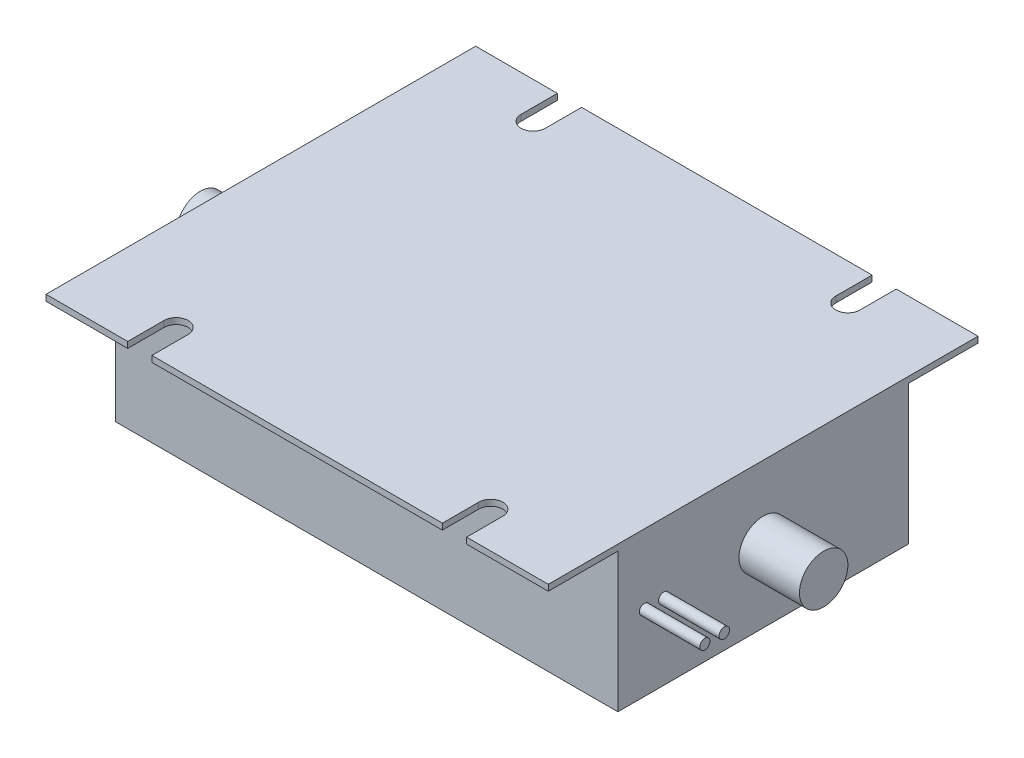
SolidWorks part; units mm, degrees
ref_plane "前基準面" through (0, 0, 0) normal (0, 0, 1) x (1, 0, 0)
ref_plane "上基準面" through (0, 0, 0) normal (0, 1, 0) x (1, 0, 0)
ref_plane "右基準面" through (0, 0, 0) normal (1, 0, 0) x (0, 0, -1)
ref_plane "平面1" through (0, 18, 0) normal (0, 1, 0) x (1, 0, 0)
sketch "草圖1" plane through (0, 18, 0) normal (0, 1, 0) x (1, 0, 0)
  line L0 (41.5, -24) -> (41.5, 24)
  line L1 (41.5, 24) -> (-41.5, 24)
  line L2 (-41.5, 24) -> (-41.5, -24)
  line L3 (-41.5, -24) -> (41.5, -24)
  line L4 (-41.5, 24) -> (41.5, -24) construction
  line L5 (41.5, 24) -> (-41.5, -24) construction
  point P4 (0, 0)
  dimension "D1" = 83
  dimension "D2" = 48
extrude "填料-伸長1" add sketch "草圖1" against normal blind 24
sketch "草圖21" plane through (0, 0, 0) normal (0, 0, -1) x (-1, 0, 0)
  line L0 (-41.5, 18) -> (41.5, 18)
  line L1 (41.5, 18) -> (41.5, 17)
  line L2 (41.5, 17) -> (-41.5, 17)
  line L3 (-41.5, 17) -> (-41.5, 18)
  line L4 (-41.5, -6) -> (-41.5, 18) construction
  line L5 (41.5, -6) -> (41.5, 18) construction
  line L6 (55, 18) -> (-55, 18) construction
  dimension "D1" = 1
extrude "填料-伸長2" add sketch "草圖21" along normal mid plane 71
sketch "草圖22" plane through (0, 18, 0) normal (0, 1, 0) x (-1, 0, 0)
  line L0 (41.5, -35.5) -> (-41.5, -35.5) construction
  line L1 (-28, -43.1015) -> (-24, -43.1015)
  line L2 (-28, -43.1015) -> (-28, -29.5)
  line L3 (-28, -29.5) -> (-24, -29.5)
  line L4 (-24, -43.1015) -> (-24, -29.5)
  line L5 (-28, -43.1015) -> (-24, -29.5) construction
  line L6 (-28, -29.5) -> (-24, -43.1015) construction
  line L7 (0, 0) -> (0, -47.7547) construction
  circle A0 centre (-26, -29.5) radius 2
  point P2 (-26, -36.3007)
  point P9 (-26, -29.5)
  line M5 (-41.5, -35.5) -> (41.5, -35.5)
  dimension "D1" = 4
  dimension "D2" = 6
  dimension "D3" = 52
extrude "除料-伸長20" cut sketch "草圖22" against normal through all contours L3 A0 | L3 A0 | A0 L2 L4 M5 region at (26, 18, -33.2629) region at (26, 18, -28.6512) region at (26, 18, -30.3488)
mirror "鏡射1" about plane through (0, 0, 0) normal (1, 0, 0) of "除料-伸長20"
mirror "鏡射2" about plane through (0, 0, 0) normal (0, 0, 1) of "鏡射1"
sketch "草圖27" plane through (-41.5, 0, 0) normal (-1, 0, 0) x (0, 0, 1)
  line L1 (55, 18) -> (-55, 18) construction
  circle A0 centre (0, 6) radius 4
  dimension "D1" = 8
  dimension "D2" = 12
extrude "填料-伸長4" add sketch "草圖27" along normal blind 10
mirror "鏡射3" about plane through (0, 0, 0) normal (1, 0, 0) of "填料-伸長4"
other "連接點1" parameters "直徑"=25.4, "殘段長度"=38.1
ref_axis "基準軸1" through (61.5, 6, 0) along (-1, 0, 0)
other "連接點2" parameters "直徑"=25.4, "殘段長度"=38.1
ref_axis "基準軸2" through (-61.5, 6, 0) along (1, 0, 0)
sketch "草圖28" plane through (41.5, 0, 0) normal (1, 0, 0) x (0, 0, -1)
  circle A0 centre (-19.6286, 6.4995) radius 0.8353
  circle A1 centre (-16.4193, 6.4995) radius 0.8666
  point P4 (-19.6286, 6.4995)
  point P5 (-16.4193, 6.4995)
extrude "填料-伸長5" add sketch "草圖28" along normal blind 10
